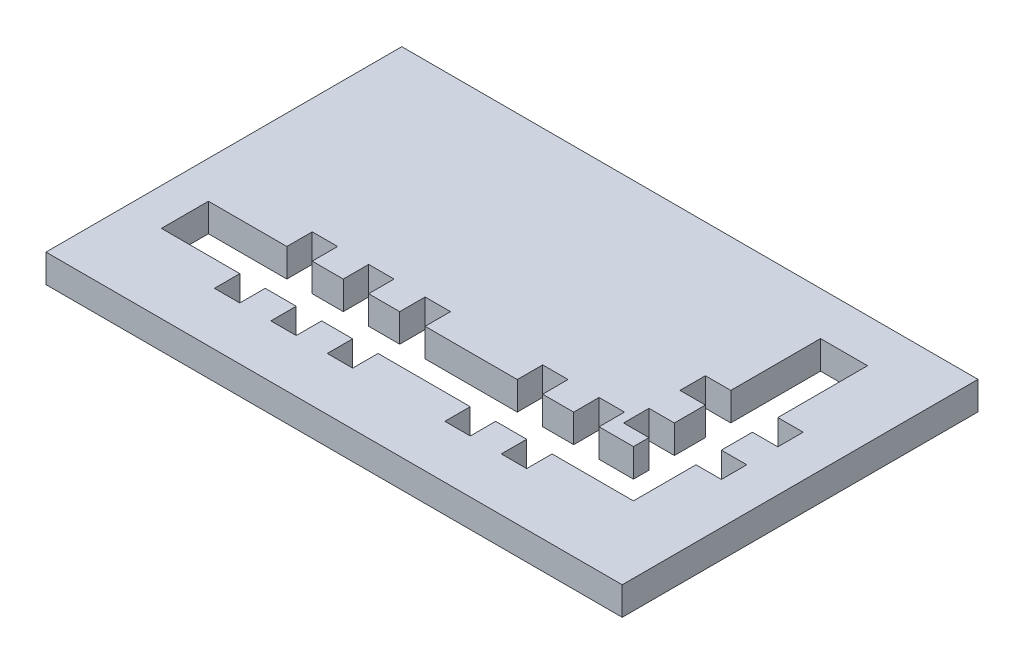
SolidWorks part; units mm, degrees
ref_plane "Front Plane" through (0, 0, 0) normal (0, 0, 1) x (1, 0, 0)
ref_plane "Top Plane" through (0, 0, 0) normal (0, 1, 0) x (1, 0, 0)
ref_plane "Right Plane" through (0, 0, 0) normal (1, 0, 0) x (0, 0, -1)
sketch "Sketch1" plane through (0, 0, 0) normal (0, 1, 0) x (1, 0, 0)
  line L1032 (-21.0164, 6.87) -> (-21.0164, 4.17)
  line L1034 (-18.3164, 6.87) -> (-18.3164, 4.17)
  line L1035 (-18.3164, 6.87) -> (-21.0164, 6.87)
  line L1036 (-15.0164, 6.87) -> (-15.0164, 4.17)
  line L1038 (-12.3164, 6.87) -> (-12.3164, 4.17)
  line L1039 (-12.3164, 6.87) -> (-15.0164, 6.87)
  line L1040 (-9.0164, 6.87) -> (-9.0164, 4.17)
  line L1042 (-6.3164, 6.87) -> (-6.3164, 4.17)
  line L1043 (-6.3164, 6.87) -> (-9.0164, 6.87)
  line L1044 (6.1836, -0.83) -> (6.1836, -3.53)
  line L1045 (6.1836, -3.53) -> (3.4836, -3.53)
  line L1046 (3.4836, -0.83) -> (3.4836, -3.53)
  line L1048 (12.1836, -0.83) -> (12.1836, -3.53)
  line L1050 (9.4836, -0.83) -> (9.4836, -3.53)
  line L1051 (9.4836, -3.53) -> (12.1836, -3.53)
  line L1053 (9.4836, 4.17) -> (9.4836, 6.87)
  line L1054 (9.4836, 6.87) -> (12.1836, 6.87)
  line L1055 (12.1836, 4.17) -> (12.1836, 6.87)
  line L1056 (3.4836, 4.17) -> (3.4836, 6.87)
  line L1058 (6.1836, 4.17) -> (6.1836, 6.87)
  line L1059 (6.1836, 6.87) -> (3.4836, 6.87)
  line L1060 (13.1336, 11.82) -> (15.8336, 11.82)
  line L1061 (13.1336, 11.82) -> (13.1336, 14.52)
  line L1062 (13.1336, 14.52) -> (15.8336, 14.52)
  line L1064 (13.1336, 8.52) -> (13.1336, 5.82)
  line L1065 (13.1336, 5.82) -> (15.8336, 5.82)
  line L1067 (13.1336, 8.52) -> (15.8336, 8.52)
  line L1068 (23.5336, 8.52) -> (20.8336, 8.52)
  line L1070 (23.5336, 5.82) -> (20.8336, 5.82)
  line L1071 (23.5336, 8.52) -> (23.5336, 5.82)
  line L1072 (23.5336, 11.82) -> (23.5336, 14.52)
  line L1073 (23.5336, 14.52) -> (20.8336, 14.52)
  line L1075 (23.5336, 11.82) -> (20.8336, 11.82)
  line L1076 (-6.3164, -3.53) -> (-9.0164, -3.53)
  line L1077 (-6.3164, -3.53) -> (-6.3164, -0.83)
  line L1079 (-9.0164, -3.53) -> (-9.0164, -0.83)
  line L1080 (-12.3164, -3.53) -> (-15.0164, -3.53)
  line L1081 (-12.3164, -3.53) -> (-12.3164, -0.83)
  line L1083 (-15.0164, -3.53) -> (-15.0164, -0.83)
  line L1084 (-18.3164, -3.53) -> (-21.0164, -3.53)
  line L1085 (-18.3164, -3.53) -> (-18.3164, -0.83)
  line L1087 (-21.0164, -3.53) -> (-21.0164, -0.83)
  line L1088 (15.8336, 11.82) -> (15.8336, 8.52)
  line L1089 (-29.3514, 4.17) -> (-21.0164, 4.17)
  line L1090 (-29.3514, 4.17) -> (-29.3514, -0.83)
  line L1091 (-29.3514, -0.83) -> (-21.0164, -0.83)
  line L1092 (20.8336, 4.17) -> (20.8336, -0.83)
  line L1093 (15.8336, 24.0625) -> (20.8336, 24.0625)
  line L1094 (15.8336, 24.0625) -> (15.8336, 14.52)
  line L1096 (20.8336, 24.0625) -> (20.8336, 14.52)
  line L1097 (20.8336, 11.82) -> (20.8336, 8.52)
  line L1098 (15.8336, 5.82) -> (15.8336, 4.17)
  line L1099 (20.8336, 5.82) -> (20.8336, 4.17)
  line L1100 (12.1836, 4.17) -> (15.8336, 4.17)
  line L1101 (12.1836, -0.83) -> (20.8336, -0.83)
  line L1102 (6.1836, 4.17) -> (9.4836, 4.17)
  line L1103 (6.1836, -0.83) -> (9.4836, -0.83)
  line L1104 (-6.3164, 4.17) -> (3.4836, 4.17)
  line L1105 (-6.3164, -0.83) -> (3.4836, -0.83)
  line L1106 (-12.3164, 4.17) -> (-9.0164, 4.17)
  line L1107 (-12.3164, -0.83) -> (-9.0164, -0.83)
  line L1108 (-18.3164, 4.17) -> (-15.0164, 4.17)
  line L1109 (-18.3164, -0.83) -> (-15.0164, -0.83)
  line L1111 (27.9594, 28.679) -> (-33.3046, 28.679)
  line L1112 (27.9594, 28.679) -> (27.9594, -9.1485)
  line L1113 (27.9594, -9.1485) -> (-33.3046, -9.1485)
  line L1114 (-33.3046, 28.679) -> (-33.3046, -9.1485)
extrude "Boss-Extrude1" add sketch "Sketch1" along normal blind 3
